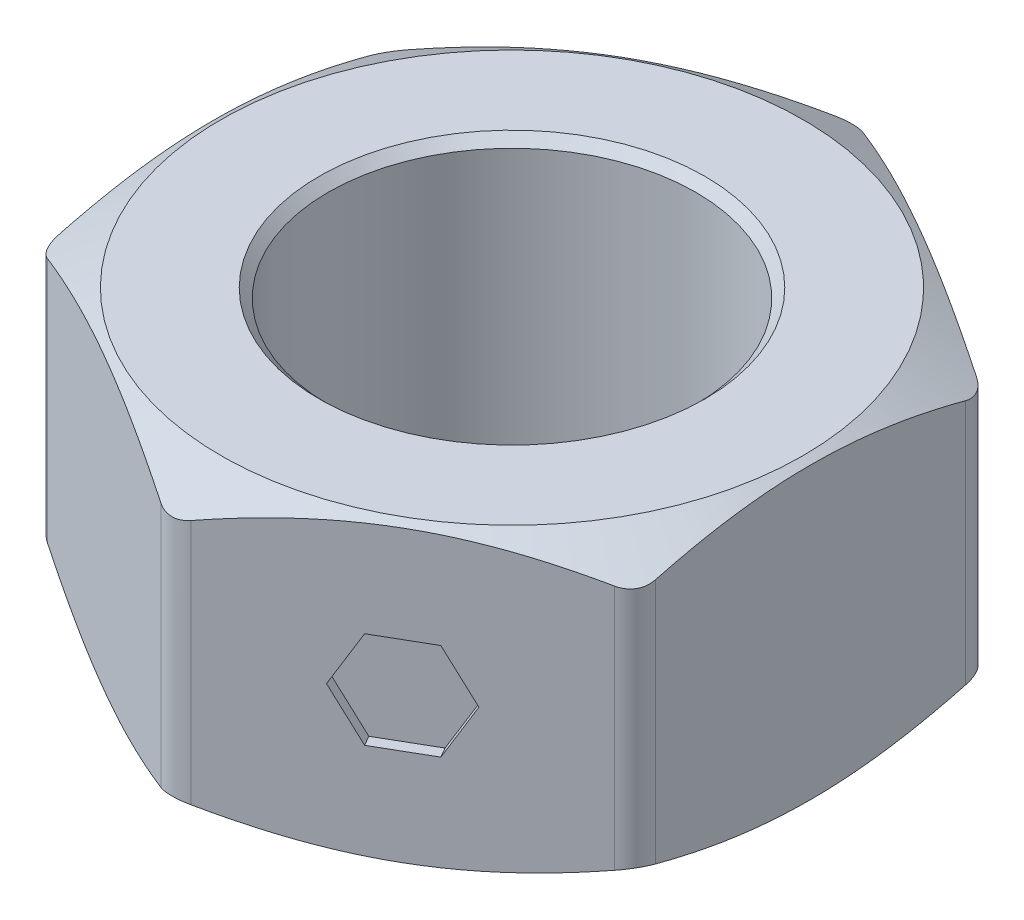
SolidWorks part; units mm, degrees
material "Alloy Steel"
ref_plane "Front Plane" through (0, 0, 0) normal (0, 0, 1) x (1, 0, 0)
ref_plane "Top Plane" through (0, 0, 0) normal (0, 1, 0) x (1, 0, 0)
ref_plane "Right Plane" through (0, 0, 0) normal (1, 0, 0) x (0, 0, -1)
sketch "Sketch1" plane through (0, 0, 0) normal (0, 0, 1) x (1, 0, 0)
  line L0 (0, -3.25) -> (0, 3.25) construction
  line L1 (6.5, 0) -> (-6.5, 0) construction
  line L2 (4, -3.25) -> (-4, -3.25) construction
  line L3 (4, -3.25) -> (4, -2) construction
  point P4 (0, 0)
  point P8 (0, 0)
  point P11 (0, -3.25)
  dimension "Height" = 6.5
  dimension "Width" = 13
  dimension "Thread Size" = 8
  dimension "Thread Pitch" = 1.25
sketch "Sketch2" plane through (0, 0, 0) normal (0, 1, 0) x (1, 0, 0)
  line L1 (0, 7.5056) -> (-6.5, 3.7528)
  line L2 (-6.5, 3.7528) -> (-6.5, -3.7528)
  line L3 (-6.5, -3.7528) -> (0, -7.5056)
  line L4 (0, -7.5056) -> (6.5, -3.7528)
  line L5 (6.5, -3.7528) -> (6.5, 3.7528)
  line L6 (6.5, 3.7528) -> (0, 7.5056)
  circle A0 centre (0, 0) radius 6.5 construction
  circle A1 centre (0, 0) radius 4
  point P19 (0, -4)
extrude "Boss-Extrude1" add sketch "Sketch2" along normal up to vertex (3.25 mm away) and the other way up to vertex (3.25 mm away) up to point (0, 3.25, 0) other way up to point (0, -3.25, 0)
fillet "Fillet1" radius 0.65 6 edges at (-6.5, 0, -3.7528) (0, 0, -7.5056) (-6.5, 0, 3.7528) (6.5, 0, -3.7528) (6.5, 0, 3.7528) (0, 0, 7.5056)
sketch "Sketch3" plane through (0, 0, 0) normal (1, 0, 0) x (0, 0, -1)
  line L2 (6.3375, -3.25) -> (7.5056, -2.5756)
  line L3 (3.9404, -3.25) -> (7.3179, -3.25) construction
  line L4 (7.5056, 3.25) -> (7.5056, -3.25) construction
  line L5 (7.5056, -2.5756) -> (7.5056, -3.25)
  line L6 (7.5056, -3.25) -> (6.3375, -3.25)
  line L12 (3.9404, 3.25) -> (7.3179, 3.25) construction
  line L16 (4, 3.25) -> (4, 3.05)
  line L17 (4, 3.25) -> (4.2, 3.25)
  line L21 (4, -3.25) -> (4, -3.05)
  line L22 (-3.3775, -3.25) -> (3.3775, -3.25) construction
  line L24 (4.2, -3.25) -> (4, -3.25)
  line L25 (4, -3.05) -> (4.2, -3.25)
  line L26 (4.2, 3.25) -> (4, 3.05)
  line L28 (0, -3.25) -> (0, 3.25) construction
  line L29 (0, -3.25) -> (0, 3.25) construction
  line L33 (6.3375, 3.25) -> (7.5056, 2.5756)
  line L34 (6.3375, 3.25) -> (6.5, 3.25) construction
  line L35 (4, 0) -> (6.5, 0) construction
  line L36 (4, -3.25) -> (4, 3.25) construction
  line L37 (3.9404, -3.25) -> (7.3179, -3.25) construction
  line L38 (6.5, 3.25) -> (6.5, 0) construction
  line L43 (7.5056, 2.5756) -> (7.5056, 3.25)
  line L47 (7.5056, 3.25) -> (6.3375, 3.25)
  point P1 (6.5, 0)
  point P14 (4, 0)
  dimension "D2" = 30
  dimension "D5" = 0.2
  dimension "D1" = 30
  dimension "D3" = 0.1625
revolve "Cut-Revolve2" cut sketch "Sketch3" angle 360 about L0
sketch "Sketch12" plane through (3.25, 0, 5.6292) normal (0.5, 0, 0.866) x (0.866, 0, -0.5)
  line L0 (0, 3.1562) -> (0, 1.0521) construction
  line L1 (0, 1.0521) -> (0, -1.0521) construction
  line L2 (0, -1.0521) -> (0, -3.1562) construction
  line L5 (-1.2148, 0) -> (-0.6074, -1.0521)
  line L6 (-0.6074, -1.0521) -> (0.6074, -1.0521)
  line L7 (0.6074, -1.0521) -> (1.2148, 0)
  line L8 (1.2148, 0) -> (0.6074, 1.0521)
  line L9 (0.6074, 1.0521) -> (-0.6074, 1.0521)
  line L10 (-0.6074, 1.0521) -> (-1.2148, 0)
  circle A0 centre (0, 0) radius 1.0521 construction
  spline S0 degree 3 poles (3.3775, 2.6798) (2.2712, 2.9743) (1.1516, 3.1551) (-0.2743, 3.1565) (-0.5618, 3.1457) (-1.1332, 3.1031) (-1.4172, 3.0713) (-2.2646, 2.9475) (-2.8233, 2.8273) (-3.3775, 2.6798) knots 0 0 0 0 0.5 0.5 0.625 0.625 0.75 0.75 1 1 1 1 construction
  spline S1 degree 3 poles (-3.3775, -2.6798) (-2.2712, -2.9743) (-1.1516, -3.1551) (0.2743, -3.1565) (0.5618, -3.1457) (1.1332, -3.1031) (1.4172, -3.0713) (2.2646, -2.9475) (2.8233, -2.8273) (3.3775, -2.6798) knots 0 0 0 0 0.5 0.5 0.625 0.625 0.75 0.75 1 1 1 1 construction
  point P9 (0, 0)
extrude "Cut-Extrude2" cut sketch "Sketch12" against normal blind 0.25
sketch "Sketch5" plane through (0, 0, 0) normal (0, 1, 0) x (1, 0, 0)
  circle A2 centre (0, 0) radius 4 construction
  point P0 (0, -4)
sketch "Sketch6" [suppressed] plane through (0, 0, 0) normal (0, 0, 1) x (1, 0, 0)
  line L0 (4, 3.25) -> (4, -3.25)
  line L2 (0, -3.25) -> (6.5, -3.25) construction
  line L3 (4, -3.25) -> (0, -3.25)
  line L4 (0, -3.25) -> (0, 3.25)
  line L5 (0, -3.25) -> (0, 3.25) construction
  line L6 (0, 3.25) -> (4, 3.25)
revolve "Revolve2" [suppressed] add sketch "Sketch6" angle 360 about L4
sketch "Sketch7" [suppressed] plane through (0, -3.25, 0) normal (0, -1, 0) x (1, 0, 0)
  circle A2 centre (0, 0) radius 4
  circle A3 centre (0, 0) radius 4
  dimension "D1" = 0
curve "Helix/Spiral1" [suppressed] pitch 1.25 height 7.75 turns 6.2
sketch "Sketch8" [suppressed] plane through (0, 0, 0) normal (0, 0, 1) x (1, 0, 0)
  line L0 (4.1353, -3.1719) -> (3.0528, -3.7969) construction
  line L1 (3.0528, -3.7969) -> (4.1353, -4.4219) construction
  line L2 (4.1353, -4.4219) -> (4.1353, -3.1719) construction
  line L3 (3.1881, -3.7187) -> (3.1881, -3.875)
  line L4 (4, -3.25) -> (4, -4.3437) construction
  line L5 (4, -3.7969) -> (4.1353, -3.7969) construction
  line L6 (3.0528, -3.7969) -> (3.1881, -3.7969) construction
  line L7 (4.0677, -3.7969) -> (4.0677, -4.3828) construction
  line L8 (3.1881, -3.7187) -> (4.1353, -3.1719)
  line L9 (4.1353, -3.1719) -> (4.0677, -4.3828)
  line L10 (3.1881, -3.875) -> (4.0677, -4.3828)
  dimension "D1" = 1.25
  dimension "D2" = 0.1562
sweep "Cut-Sweep1" [suppressed] cut profiles "Sketch8" path "Helix/Spiral1"
sketch "Sketch9" [suppressed] plane through (0, 0, 0) normal (0, 0, 1) x (1, 0, 0)
  line L0 (0, 0.75) -> (0, -3.25)
  line L1 (0, 0.75) -> (0, 0.95)
  line L2 (0, -3.25) -> (4, -3.25)
  line L3 (4, -3.25) -> (4.2, -3.25)
  line L4 (4.2, -3.25) -> (0, 0.95)
  dimension "D1" = 0.2
revolve "Revolve3" [suppressed] add sketch "Sketch9" angle 360 about L0
sketch "Sketch11" [suppressed] plane through (0, 0, 0) normal (0, 0, 1) x (1, 0, 0)
  line L0 (0, 3.25) -> (0, -0.4375)
  line L1 (0, -3.25) -> (0, 3.25) construction
  line L2 (0, -0.4375) -> (4.2, 3.25)
  line L3 (4.2, 3.25) -> (0, 3.25)
  spline S0 degree 2 poles (-1.1661, -2.2381) (-1.7845, -2.1956) (-2.2543, -2.1562) (-3.1881, -2.0781) (-3.1881, -2) (-3.1881, -1.9219) (-2.2543, -1.8437) (-1.3206, -1.7656) (0, -1.6875) (1.3206, -1.6094) (2.2543, -1.5312) (3.1881, -1.4531) (3.1881, -1.375) (3.1881, -1.2969) (2.2543, -1.2187) (1.3206, -1.1406) (0, -1.0625) (-1.3206, -0.9844) (-2.2543, -0.9062) (-3.1881, -0.8281) (-3.1881, -0.75) (-3.1881, -0.6719) (-2.2543, -0.5937) (-1.3206, -0.5156) (0, -0.4375) (1.3206, -0.3594) (2.2543, -0.2812) (3.1881, -0.2031) (3.1881, -0.125) (3.1881, -0.0469) (2.2543, 0.0313) (1.3206, 0.1094) (0, 0.1875) (-1.3206, 0.2656) (-2.2543, 0.3438) (-3.1881, 0.4219) (-3.1881, 0.5) (-3.1881, 0.5781) (-2.2543, 0.6563) (-1.3206, 0.7344) (0, 0.8125) (1.3206, 0.8906) (2.2543, 0.9688) (3.1881, 1.0469) (3.1881, 1.125) (3.1881, 1.2031) (2.2543, 1.2813) (1.3206, 1.3594) (0, 1.4375) (-1.3206, 1.5156) (-2.2543, 1.5938) (-3.1881, 1.6719) (-3.1881, 1.75) (-3.1881, 1.8281) (-2.2543, 1.9063) (-1.3206, 1.9844) (0, 2.0625) (1.3206, 2.1406) (2.2543, 2.2188) (3.1881, 2.2969) (3.1881, 2.375) (3.1881, 2.4531) (2.2543, 2.5313) (1.3206, 2.6094) (0, 2.6875) (-1.3206, 2.7656) (-2.2543, 2.8438) (-3.1881, 2.9219) (-3.1881, 3) (-3.1881, 3.0781) (-2.2543, 3.1563) (-1.7154, 3.2013) (-0.991, 3.25) knots 0.288704 0.288704 0.288704 0.296875 0.296875 0.3125 0.3125 0.328125 0.328125 0.34375 0.34375 0.359375 0.359375 0.375 0.375 0.390625 0.390625 0.40625 0.40625 0.421875 0.421875 0.4375 0.4375 0.453125 0.453125 0.46875 0.46875 0.484375 0.484375 0.5 0.5 0.515625 0.515625 0.53125 0.53125 0.546875 0.546875 0.5625 0.5625 0.578125 0.578125 0.59375 0.59375 0.609375 0.609375 0.625 0.625 0.640625 0.640625 0.65625 0.65625 0.671875 0.671875 0.6875 0.6875 0.703125 0.703125 0.71875 0.71875 0.734375 0.734375 0.75 0.75 0.765625 0.765625 0.78125 0.78125 0.796875 0.796875 0.8125 0.8125 0.828125 0.828125 0.837443 0.837443 0.837443 weights 0.96202 0.960193 1 0.92388 1 0.92388 1 0.92388 1 0.92388 1 0.92388 1 0.92388 1 0.92388 1 0.92388 1 0.92388 1 0.92388 1 0.92388 1 0.92388 1 0.92388 1 0.92388 1 0.92388 1 0.92388 1 0.92388 1 0.92388 1 0.92388 1 0.92388 1 0.92388 1 0.92388 1 0.92388 1 0.92388 1 0.92388 1 0.92388 1 0.92388 1 0.92388 1 0.92388 1 0.92388 1 0.92388 1 0.92388 1 0.92388 1 0.92388 1 0.954607 0.963353 construction
revolve "Revolve4" [suppressed] add sketch "Sketch11" angle 360 about L0
sketch "Sketch10" [suppressed] plane through (0, -3.25, 0) normal (0, -1, 0) x (1, 0, 0)
  circle A0 centre (0, 0) radius 4.2 construction
  circle A1 centre (0, 0) radius 4.2
extrude "Boss-Extrude2" [suppressed] add sketch "Sketch10" against normal up to surface (6.5 mm away)
combine bodies "Combine1" [suppressed] operation type add bodies to combine 110 112
equation "\"D5@Sketch3\"=\"Thread Size@Sketch1\"*.025"
equation "\"D4@Helix/Spiral1\" = \"Thread Pitch@Sketch1\""
equation "\"D3@Helix/Spiral1\"=\"Height@Sketch1\"+\"Thread Pitch@Sketch1\""
equation "\"D1@Sketch8\" = \"Thread Pitch@Sketch1\""
equation "\"D2@Sketch8\" = \"Thread Pitch@Sketch1\" / 8"
equation "\"D1@Sketch9\"=\"Thread Size@Sketch1\" * .025"
equation "\"D1@Fillet1\"=\"Width@Sketch1\" * .05"
equation "\"D3@Sketch3\"=\"Width@Sketch1\"*.0125"
equation "\"D1@Cut-Extrude2\"=((\"Width@Sketch1\"-\"Thread Size@Sketch1\")/2)*.1"
